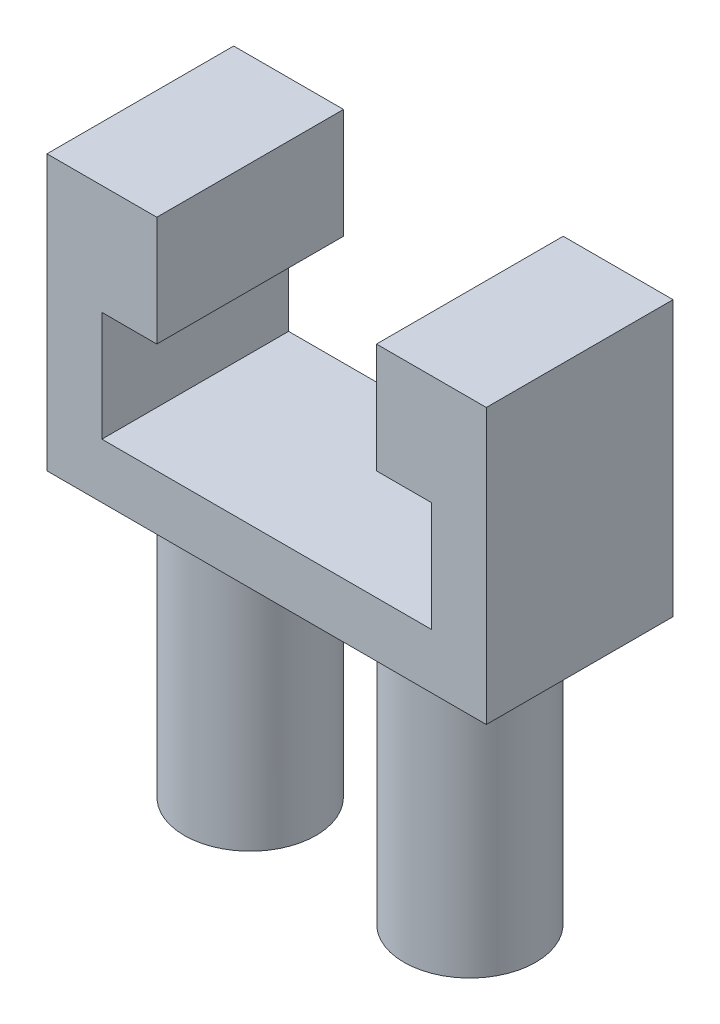
SolidWorks part; units mm, degrees
ref_plane "前视基准面" through (0, 0, 0) normal (0, 0, 1) x (1, 0, 0)
ref_plane "上视基准面" through (0, 0, 0) normal (0, 1, 0) x (1, 0, 0)
ref_plane "右视基准面" through (0, 0, 0) normal (1, 0, 0) x (0, 0, -1)
sketch "草图3" plane through (0, 0, 0) normal (0, 1, 0) x (1, 0, 0)
  line L1 (0, 0) -> (32, 0)
  line L2 (0, 0) -> (0, 12)
  line L3 (0, 12) -> (32, 12)
  line L4 (32, 0) -> (32, 12)
extrude "凸台-拉伸3" add sketch "草图3" along normal blind 5
sketch "草图4" plane through (0, 0, 0) normal (0, -1, 0) x (1, 0, 0)
  circle A0 centre (6, -6) radius 5
  circle A1 centre (26, -6) radius 5
extrude "凸台-拉伸4" add sketch "草图4" along normal blind 10
sketch "草图6" plane through (0, -10, 0) normal (0, -1, 0) x (1, 0, 0)
  circle A0 centre (26, -6) radius 2.5
sketch "草图8" plane through (0, -10, 0) normal (0, -1, 0) x (1, 0, 0)
  circle A1 centre (6, -6) radius 5
extrude "凸台-拉伸6" add sketch "草图8" along normal blind 5
sketch "草图9" plane through (0, -15, 0) normal (0, -1, 0) x (1, 0, 0)
  circle A0 centre (6, -6) radius 4.8
  dimension "D1" = 9.6
ref_plane "基准面4" through (0, 0, -6) normal (0, 0, 1) x (1, 0, 0)
sketch "草图13" plane through (0, 0, -6) normal (0, 0, 1) x (1, 0, 0)
  line L2 (1, -15) -> (11, -15) construction
  line L4 (1.2213, -14.5) -> (1.0213, -15)
  line L5 (6, -15) -> (6, 7.7228)
  line L6 (1.2, -15) -> (10.8, -15) construction
  line L7 (1.0213, -15) -> (1.2213, -15)
  line L8 (1.2213, -15) -> (1.2213, -14.5)
  line L9 (1.2213, -14.5) -> (1.2213, -15)
  line L10 (1.2213, -15) -> (1.0213, -15)
  line L11 (1.0213, -15) -> (1.2213, -14.5)
  dimension "D1" = 0.5385
extrude "切除-拉伸2" cut sketch "草图9" against normal blind 0.5
sketch "草图14" plane through (0, 0, -6) normal (0, 0, 1) x (1, 0, 0)
  line L0 (1.2213, -15) -> (1.0213, -15)
  line L1 (1.0213, -15) -> (1.0213, -20)
  line L2 (1.0213, -20) -> (1.2213, -15)
  line L3 (6, -15) -> (6, -18.9564)
revolve "旋转2" add sketch "草图14" angle 360 about L5 region at (1.0879, -16.6667, -6)
sketch "草图16" plane through (0, -10, 0) normal (0, -1, 0) x (1, 0, 0)
  circle A0 centre (26, -6) radius 5
sketch "草图35" plane through (0, -10, 0) normal (0, -1, 0) x (1, 0, 0)
  circle A0 centre (26, -6) radius 2.5
sketch "草图22" plane through (0, -10, 0) normal (0, -1, 0) x (1, 0, 0)
  circle A0 centre (26, -6) radius 2.5
sketch "草图24" plane through (0, 0, -6) normal (0, 0, 1) x (1, 0, 0)
  line L0 (0, 0) -> (10, 0)
  line L1 (0, 0) -> (32, 0) construction
  line L2 (10, 0) -> (10, 1)
  line L3 (10, 1) -> (10, 3)
  line L4 (10, 1) -> (22, 1)
  line L5 (22, 1) -> (22, 3)
  line L6 (13.5, 3) -> (13.5, 5)
  line L7 (0, 5) -> (32, 5) construction
  line L8 (10, 3) -> (13.5, 3)
  line L11 (22, 3) -> (18.5, 3)
  line L12 (18.5, 3) -> (18.5, 5)
  line L13 (18.5, 5) -> (13.5, 5)
  dimension "D1" = 12
  dimension "D2" = 2
ref_plane "基准面7" through (0, -20, 0) normal (0, 1, 0) x (1, 0, 0)
sketch "草图36" plane through (0, -20, 0) normal (0, 1, 0) x (1, 0, 0)
  circle A1 centre (6, 6) radius 5
  circle A2 centre (6, 6) radius 4.98
extrude "凸台-拉伸11" add sketch "草图36" along normal blind 5
sketch "草图39" plane through (0, 0, -6) normal (0, 0, 1) x (1, 0, 0)
  line L0 (1, 0) -> (1, -16)
  line L1 (1, 0) -> (1, -20) construction
  line L2 (11, 0) -> (11, -16)
  line L3 (11, -20) -> (11, 0) construction
sketch "草图42" plane through (0, -20, 0) normal (0, 1, 0) x (1, 0, 0)
  circle A0 centre (6, 6) radius 1.5
sketch "草图45" plane through (0, 0, 0) normal (0, 0, 1) x (1, 0, 0)
  line L0 (0, 5) -> (1, 5)
  line L1 (0, 5) -> (32, 5) construction
sketch "草图46" plane through (0, 5, 0) normal (0, 1, 0) x (1, 0, 0)
  line L0 (0, 12) -> (0, 0)
  line L1 (0, 0) -> (32, 0)
  line L2 (32, 0) -> (32, 12)
  line L3 (32, 12) -> (0, 12)
extrude "凸台-拉伸12" add sketch "草图46" along normal blind 20
sketch "草图47" plane through (0, 0, 0) normal (0, 0, 1) x (1, 0, 0)
  line L0 (26, 0) -> (36, 0)
  line L1 (21, 0) -> (31, 0) construction
  line L2 (6, 0) -> (-4, 0)
  line L3 (1, 0) -> (11, 0) construction
  line L4 (-4, 0) -> (-4, 25)
  line L5 (-4, 25) -> (0, 25)
  line L6 (32, 25) -> (36, 25)
  line L7 (36, 25) -> (36, 0)
  line L8 (0, 25) -> (0, 0)
  line L9 (32, 25) -> (32, 0)
  line M6 (0, 25) -> (0, 0)
extrude "凸台-拉伸13" add sketch "草图47" against normal blind 12 contours L5 L4 L2 M6 region at (-2, 12.5, 0)
sketch "草图48" plane through (0, 0, 0) normal (0, 0, 1) x (1, 0, 0)
  line L0 (26, 0) -> (36, 0)
  line L1 (21, 0) -> (31, 0) construction
  line L2 (36, 0) -> (36, 25)
  line L3 (36, 25) -> (32, 25)
  line L4 (32, 25) -> (32, 0)
  line M6 (32, 0) -> (32, 25)
extrude "凸台-拉伸14" add sketch "草图48" against normal blind 12 contours L2 L3 L0 M6 region at (34, 12.5, 0)
sketch "草图49" plane through (0, 0, 0) normal (0, 0, 1) x (1, 0, 0)
  line L1 (1, 5) -> (1, 15)
  line L2 (1, 5) -> (31, 5)
  line L3 (31, 5) -> (31, 15)
  line L4 (31, 15) -> (26, 15)
  line L5 (26, 15) -> (26, 25)
  line L6 (-4, 25) -> (36, 25) construction
  line L7 (1, 15) -> (6, 15)
  line L8 (6, 15) -> (6, 25)
extrude "切除-拉伸5" cut sketch "草图49" against normal blind 12 and the other way through all flip side to cut
sketch "草图50" plane through (0, 0, 0) normal (0, -1, 0) x (1, 0, 0)
  circle A1 centre (6, -6) radius 6
extrude "凸台-拉伸15" add sketch "草图50" along normal blind 20
sketch "草图51" plane through (0, 0, 0) normal (0, -1, 0) x (1, 0, 0)
  circle A0 centre (26, -6) radius 6
extrude "凸台-拉伸16" add sketch "草图51" along normal blind 20
sketch "草图52" plane through (0, 0, -6) normal (0, 0, 1) x (1, 0, 0)
  line L0 (0, -20) -> (0, -25)
  line L3 (12, -20) -> (12, -25)
  line L5 (0, -20) -> (0.2, -20)
  line L6 (0.2, -20) -> (0, -25)
  line L7 (6, -20) -> (6, -27.9108)
  line L8 (0, -20) -> (12, -20) construction
revolve "旋转3" add sketch "草图52" angle 360 about L7
sketch "草图53" plane through (0, 0, -6) normal (0, 0, 1) x (1, 0, 0)
  line L0 (20, -20) -> (20, -25)
  line L1 (20, -20) -> (20.2, -20)
  line L2 (20, -20) -> (32, -20) construction
  line L3 (20, -25) -> (20.2, -20)
  line L4 (26, -20) -> (26, -27.9889)
revolve "旋转4" add sketch "草图53" angle 360 about L4
sketch "草图55" plane through (0, 0, 0) normal (0, 0, 1) x (1, 0, 0)
  line L0 (-4, 25) -> (6, 25)
  line L1 (6, 25) -> (6, 15)
  line L2 (6, 15) -> (1, 15)
  line L3 (1, 15) -> (1, 5)
  line L4 (1, 5) -> (31, 5)
  line L5 (31, 5) -> (31, 15)
  line L6 (31, 15) -> (26, 15)
  line L7 (26, 15) -> (26, 25)
  line L8 (26, 25) -> (36, 25)
  line L9 (36, 25) -> (36, 0)
  line L10 (36, 0) -> (-4, 0)
  line L11 (-4, 0) -> (-4, 25)
extrude "凸台-拉伸17" add sketch "草图55" along normal blind 2.5
sketch "草图56" plane through (0, 0, -12) normal (0, 0, -1) x (-1, 0, 0)
  line L0 (-36, 25) -> (-26, 25)
  line L1 (-26, 25) -> (-26, 15)
  line L2 (-26, 15) -> (-31, 15)
  line L3 (-31, 15) -> (-31, 5)
  line L4 (-31, 5) -> (-1, 5)
  line L5 (-1, 5) -> (-1, 15)
  line L6 (-1, 15) -> (-6, 15)
  line L7 (-6, 15) -> (-6, 25)
  line L8 (-6, 25) -> (4, 25)
  line L9 (4, 25) -> (4, 0)
  line L10 (4, 0) -> (-36, 0)
  line L11 (-36, 0) -> (-36, 25)
extrude "凸台-拉伸18" add sketch "草图56" along normal blind 2.5
